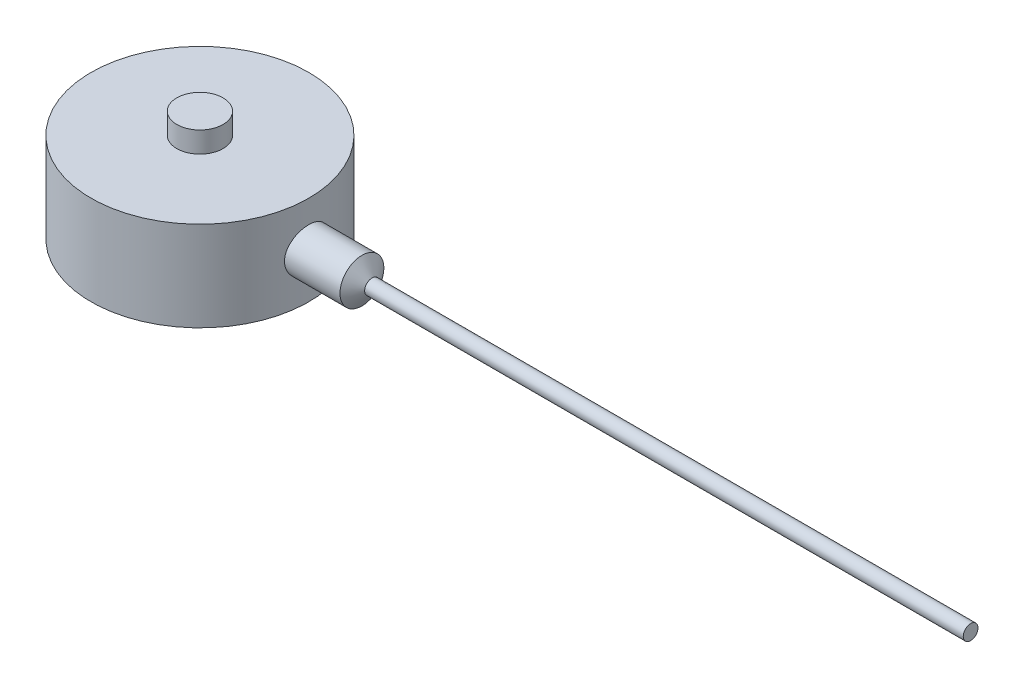
SolidWorks part; units mm, degrees
ref_plane "Front Plane" through (0, 0, 0) normal (0, 0, 1) x (1, 0, 0)
ref_plane "Top Plane" through (0, 0, 0) normal (0, 1, 0) x (1, 0, 0)
ref_plane "Right Plane" through (0, 0, 0) normal (1, 0, 0) x (0, 0, -1)
sketch "Sketch1" plane through (0, 0, 0) normal (0, 1, 0) x (1, 0, 0)
  circle A0 centre (0, 0) radius 25
  dimension "D1" = 50
extrude "base" add sketch "Sketch1" along normal blind 20.6
sketch "Sketch2" plane through (0, 20.6, 0) normal (0, 1, 0) x (1, 0, 0)
  circle A0 centre (0, 0) radius 5.3
  dimension "D1" = 10.6
extrude "button" add sketch "Sketch2" along normal blind 4.8
sketch "Sketch3" plane through (0, 0, 0) normal (0, 0, 1) x (1, 0, 0)
  line L0 (25, 10.3) -> (176.8624, 10.3) construction
  line L1 (25, 0) -> (25, 20.6) construction
  line L2 (25, 15.3355) -> (37.1737, 15.3355)
  line L3 (37.1737, 15.3355) -> (39.4984, 11.9964)
  line L4 (25, 10.3) -> (25, 15.3355) construction
  line L5 (39.4984, 11.9964) -> (176.8624, 11.9964)
  line L6 (176.8624, 11.9964) -> (176.8624, 10.3)
  line L7 (25, 10.3) -> (176.8624, 10.3)
  line L8 (25, 15.3355) -> (23.4807, 15.3355)
  line L9 (23.4807, 15.3355) -> (23.4807, 10.3)
  line L10 (23.4807, 10.3) -> (25, 10.3)
  point P9 (176.8624, 11.9964)
revolve "cable" add sketch "Sketch3" angle 360 about L0
